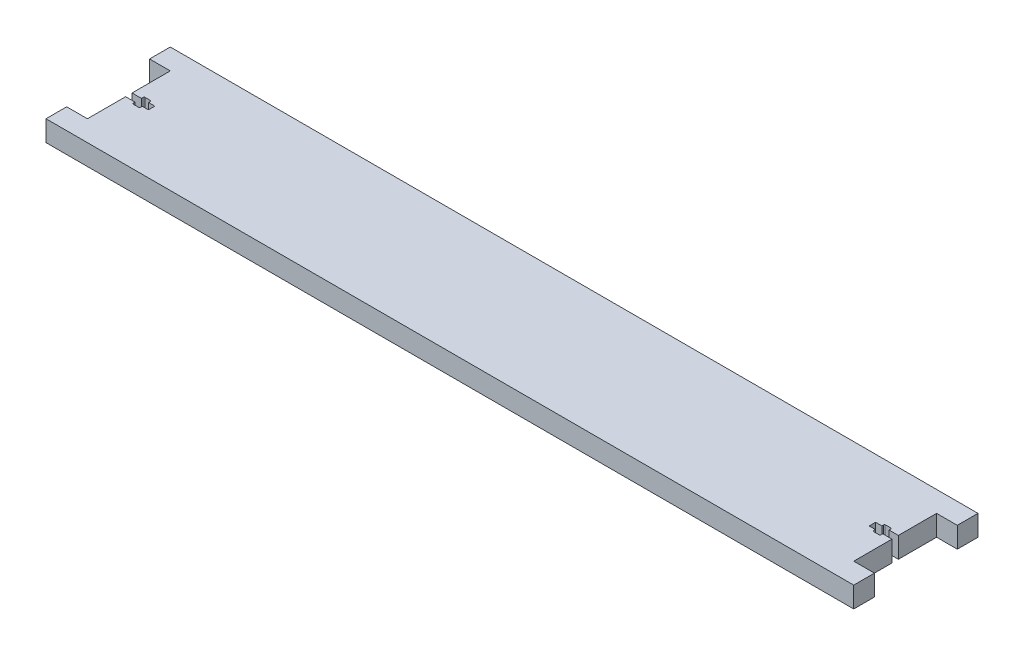
SolidWorks part; units mm, degrees
ref_plane "Front Plane" through (0, 0, 0) normal (0, 0, 1) x (1, 0, 0)
ref_plane "Top Plane" through (0, 0, 0) normal (0, 1, 0) x (1, 0, 0)
ref_plane "Right Plane" through (0, 0, 0) normal (1, 0, 0) x (0, 0, -1)
sketch "Sketch1" plane through (0, 0, 0) normal (0, 1, 0) x (1, 0, 0)
  line L1 (-185, 30) -> (185, 30)
  line L2 (-185, 30) -> (-185, -30)
  line L3 (-185, -30) -> (185, -30)
  line L4 (185, 30) -> (185, -30)
  line L5 (-185, 30) -> (185, -30) construction
  line L6 (-185, -30) -> (185, 30) construction
  point P0 (0, 0)
  dimension "D1" = 370
  dimension "D2" = 60
extrude "Boss-Extrude1" add sketch "Sketch1" along normal blind 10
sketch "Sketch2" plane through (0, 10, 0) normal (0, 1, 0) x (1, 0, 0)
  line L0 (185, 0) -> (204.4903, 0) construction
  line L1 (185, -30) -> (185, 30) construction
  line L2 (185, 30) -> (195, 30)
  line L3 (195, 30) -> (195, 20)
  line L4 (195, 20) -> (185, 20)
  line L5 (185, 20) -> (185, 30)
  line L6 (185, -20) -> (185, -30)
  line L7 (195, -20) -> (185, -20)
  line L8 (195, -30) -> (195, -20)
  line L9 (185, -30) -> (195, -30)
  line L10 (195, 25) -> (185, 25) construction
  line L11 (195, -25) -> (185, -25) construction
  dimension "D1" = 10
  dimension "D2" = 10
extrude "Boss-Extrude2" add sketch "Sketch2" against normal through all
sketch "Sketch3" plane through (0, 10, 0) normal (0, 1, 0) x (1, 0, 0)
  line L0 (185, 0) -> (174, 0) construction
  line L1 (185, -20) -> (185, 20) construction
  line L2 (185, 1.55) -> (174, 1.55) construction
  line L3 (185, -1.55) -> (185, 1.55)
  line L4 (185, 1.55) -> (180.5, 1.55)
  line L5 (180.5, 1.55) -> (180.5, 2.35)
  line L6 (180, 2.85) -> (177.5, 2.85)
  line L7 (177, 2.35) -> (177, 1.55)
  line L8 (177, 1.55) -> (174, 1.55)
  line L9 (174, 1.55) -> (174, -1.55)
  line L10 (185, -1.55) -> (174, -1.55) construction
  line L11 (177, -1.55) -> (174, -1.55)
  line L12 (177, -2.35) -> (177, -1.55)
  line L13 (180, -2.85) -> (177.5, -2.85)
  line L14 (180.5, -1.55) -> (180.5, -2.35)
  line L15 (185, -1.55) -> (180.5, -1.55)
  arc A0 (180.5, 2.35) -> (180, 2.85) centre (180, 2.35) ccw
  arc A1 (177.5, 2.85) -> (177, 2.35) centre (177.5, 2.35) ccw
  arc A2 (177.5, -2.85) -> (177, -2.35) centre (177.5, -2.35) cw
  arc A3 (180.5, -2.35) -> (180, -2.85) centre (180, -2.35) cw
  point P13 (180.5, 2.85)
  point P16 (177, 2.85)
  point P27 (177, -2.85)
  point P28 (180.5, -2.85)
  dimension "D6" = 0.5
  dimension "D1" = 11
  dimension "D2" = 1.55
  dimension "D3" = 3.5
  dimension "D4" = 2.85
  dimension "D5" = 8
extrude "Cut-Extrude1" cut sketch "Sketch3" against normal through all
mirror "Mirror1" about plane through (0, 0, 0) normal (1, 0, 0) of "Cut-Extrude1", "Boss-Extrude2"
equation "\"X-ROD-SPACING\"=45"
equation "\"Y-ROD-SPACING\"=75"
equation "\"Z-ROD-SPACING\"=17.5"
equation "\"Y-BED-OFFSET\"=2"
equation "\"Y-BED-ROD-INSET\"=3.5"
equation "\"Y-BED-SCREW-SPACING\"=209"
equation "\"Y-BED-SCREW-CUTOUT-SLOT-HEIGHT\"=2.5"
equation "\"T-SLOT-NUT-FILLET-RADIUS\"=0.5"
equation "\"T-SLOT-SCREW-SHAFT-RADIUS\"=1.55"
equation "\"T-SLOT-SCREW-SHAFT-CUTOUT-LENGTH\"=11"
equation "\"T-SLOT-NUT-DEPTH\"=3.5"
equation "\"T-SLOT-NUT-WIDTH\"=2.85"
equation "\"T-SLOT-NUT-END-DISTANCE\"=8"
equation "\"ACRYLIC-THICKNESS\"=10"
equation "\"ACRYLIC-THICKNESS2\"=4.5"
equation "\"ACRYLIC-TAB-CUTOUT-SIZE\"=\"ACRYLIC-THICKNESS\"+\"ACRYLIC-TAB-TOLERANCE\"*2"
equation "\"ACRYLIC-TAB-TOLERANCE\"=-.05"
equation "\"KERF\"=0.075"
equation "\"ACRYLIC-THICKNESS-TAB-CUTOUT-WIDTH\"=\"ACRYLIC-THICKNESS\"-\"KERF\"*2"
equation "\"ACRYLIC-THICKNESS-TAB-CUTOUT-HEIGHT\"=\"ACRYLIC-TAB-WIDTH\"-\"KERF\"*4"
equation "\"ACRYLIC-THICKNESS2-TAB-CUTOUT-WIDTH\"=\"ACRYLIC-THICKNESS2\"-\"KERF\"*2"
equation "\"ACRYLIC-THICKNESS2-TAB-CUTOUT-HEIGHT\"=\"ACRYLIC-TAB-WIDTH\"-\"KERF\"*4"
equation "\"ACRYLIC-TAB-WIDTH\"=\"ACRYLIC-THICKNESS\""
equation "\"ACRYLIC-M3-HOLE\"=2.9"
equation "\"SMOOTHROD-CAP-SCREW-DISTANCE\"=20"
equation "\"FRAME-WIDTH-INNER\"=370"
equation "\"NEMA17-HOLE-SPACING\"=31"
equation "\"NEMA17-CENTRAL-CUTOUT\"=22.5"
equation "\"Z-BRACKET-REACH\"=57"
equation "\"Z-ROD-INSET\"=13.5"
equation "\"TOP-BRACKET-SPACING\"=40"
equation "\"SMOOTHROD-X-LENGTH\"=350"
equation "\"SMOOTHROD-Y-LENGTH\"=350"
equation "\"SMOOTHROD-Z-LENGTH\"=350"
equation "\"SMOOTHROD-TIGHTENING-HEADROOM\"=.25"
equation "\"LEADSCREW-Z-LENGTH\"=300"
equation "\"SCREW-LENGTH-FRAME\"=\"ACRYLIC-THICKNESS\" + 10"
equation "\"SCREW-LENGTH-MOTOR\"=\"ACRYLIC-THICKNESS\" + 5"
equation "\"SCREW-LENGTH-EXTRUDER\"=28"
equation "\"SCREW-HEAD-RADIUS\"=6"
equation "\"PRINTED-M3-HOLE\"=3.5"
equation "\"PRINTED-X-SMOOTHROD-DIAMETER\"=8.8"
equation "\"PRINTED-X-SMOOTHROD-CUTOUT\"=10"
equation "\"PRINTED-X-BASE-HEIGHT\"=10"
equation "\"PRINTED-LM8UU-CUTOUT-SIZE\"=15.5"
equation "\"PRINTED-LM8UU-CUTOUT-LENGTH\"=24.5"
equation "\"PRINTED-X-IDLER-HEIGHT\"=16"
equation "\"PRINTED-M3-NUT-AF\"=6.25"
equation "\"PSU-MOUNTING-WIDTH\"=95"
equation "\"PSU-MOUNTING-HEIGHT\"=177"
equation "\"Y-BELT-TO-ROD-DISTANCE\"=20"
equation "\"SPOOL-HOLDER-ROD-SPACING\"=150"
equation "\"ACRYLIC-X-CARRIAGE-WIDTH\"=55"
equation "\"ACRYLIC-X-CARRIAGE-HEIGHT\"=75"
equation "\"ACRYLIC-X-CARRIAGE-LM8UU-CUTOUT-WIDTH\"=24.25"
equation "\"ACRYLIC-X-CARRIAGE-LM8UU-CUTOUT-HEIGHT\"=11.0"
equation "\"ACRYLIC-X-CARRIAGE-SCREW-SPACING-X\"=15"
equation "\"ACRYLIC-X-CARRIAGE-SCREW-SPACING-Y\"=33"
equation "\"ACRYLIC-X-CARRIAGE-CENTER-TAB-SPACING\"=14"
equation "\"ACRYLIC-X-CARRIAGE-EXTRUDER-OFFSET\"=26"
equation "\"ACRYLIC-X-CARRIAGE-EXTRUDER-ANGLE\"=90"
equation "\"ACRYLIC-X-CARRIAGE-EXTRUDER-SHELF-DEPTH\"=\"ACRYLIC-X-CARRIAGE-EXTRUDER-OFFSET\" + 28"
equation "\"ACRYLIC-X-CARRIAGE-EXTRUDER-BRACE-SPACING\"=23"
equation "\"ACRYLIC-X-CARRIAGE-EXTRUDER-BRACE-TAB-OFFSET\"=20"
equation "\"ACRYLIC-X-CARRIAGE-EXTRUDER-BRACE-HEIGHT\"=35"
equation "\"ACRYLIC-X-CARRIAGE-EXTRUDER-BRACE-SCREW-SPACING\"=22"
equation "\"ACRYLIC-X-CARRIAGE-DUAL-WIDTH-MULTIPLIER\"=1.65"
equation "\"ACRYLIC-X-CARRIAGE-DUAL-HOTEND-SPACING\"=42"
equation "\"ACRYLIC-X-CARRIAGE-DUAL-WIDTH\"=75"
equation "\"ACRYLIC-X-CARRIAGE-DUAL-FAN-OFFSET\"=52"
equation "\"ACRYLIC-X-CARRIAGE-DUAL-FAN-HEIGHT\"=20"
equation "\"ACRYLIC-X-CARRIAGE-DUAL-HOTEND-SEPARATION\"=36"
equation "\"ACRYLIC-X-CARRIAGE-DUAL-MOUNT-PLATE-DEPTH\"=75"
equation "\"ACRYLIC-X-CARRIAGE-DUAL-MOUNT-BRACE-WIDTH\"=33"
equation "\"ACRYLIC-X-CARRIAGE-DUAL-MOUNT-SCREW-WIDTH\"=40"
equation "\"BLOWER-FAN-WIDTH\"=15"
equation "\"D1@Sketch1\"=\"FRAME-WIDTH-INNER\""
equation "\"D1@Boss-Extrude1\"=\"ACRYLIC-THICKNESS\""
equation "\"D2@Sketch2\"=\"ACRYLIC-THICKNESS\""
equation "\"D1@Sketch3\"=\"T-SLOT-SCREW-SHAFT-CUTOUT-LENGTH\""
equation "\"D2@Sketch3\"=\"T-SLOT-SCREW-SHAFT-RADIUS\""
equation "\"D3@Sketch3\"=\"T-SLOT-NUT-DEPTH\""
equation "\"D4@Sketch3\"=\"T-SLOT-NUT-WIDTH\""
equation "\"D5@Sketch3\"=\"T-SLOT-NUT-END-DISTANCE\""
equation "\"D6@Sketch3\"=\"T-SLOT-NUT-FILLET-RADIUS\""
